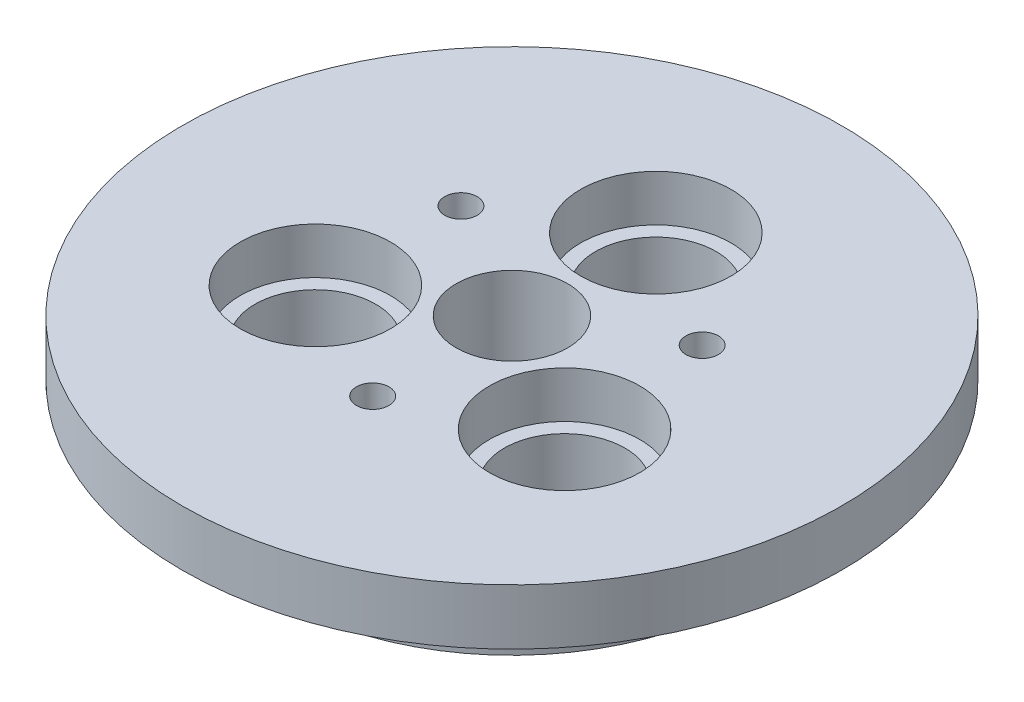
SolidWorks part; units mm, degrees
ref_plane "Front Plane" through (0, 0, 0) normal (0, 0, 1) x (1, 0, 0)
ref_plane "Top Plane" through (0, 0, 0) normal (0, 1, 0) x (1, 0, 0)
ref_plane "Right Plane" through (0, 0, 0) normal (1, 0, 0) x (0, 0, -1)
sketch "Sketch1" plane through (0, 0, 0) normal (0, 1, 0) x (1, 0, 0)
  circle A0 centre (0, 0) radius 35.5
  dimension "D1" = 71
extrude "Boss-Extrude1" add sketch "Sketch1" along normal mid plane 6
sketch "Sketch2" plane through (0, 3, 0) normal (0, 1, 0) x (1, 0, 0)
  circle A0 centre (0, 0) radius 26
  dimension "D1" = 52
extrude "Boss-Extrude2" add sketch "Sketch2" along normal blind 1
sketch "Sketch3" plane through (0, 4, 0) normal (0, 1, 0) x (1, 0, 0)
  circle A0 centre (0, 0) radius 25
  dimension "D1" = 50
extrude "Boss-Extrude3" add sketch "Sketch3" along normal blind 19
sketch "Sketch4" plane through (0, 23, 0) normal (0, 1, 0) x (1, 0, 0)
  line L0 (0, 15.5) -> (0, 0) construction
  line L1 (0, 0) -> (-13.4234, -7.75) construction
  circle A0 centre (0, 15.5) radius 12
  circle A1 centre (13.4234, -7.75) radius 12
  circle A2 centre (-13.4234, -7.75) radius 12
  dimension "D1" = 24
  dimension "D2" = 15.5
  dimension "D3" = 3
extrude "Cut-Extrude1" [suppressed] cut sketch "Sketch4" against normal through all
sketch "Sketch5" plane through (0, 23, 0) normal (0, 1, 0) x (1, 0, 0)
  circle A0 centre (0, 0) radius 6
  dimension "D1" = 12
extrude "Cut-Extrude2" cut sketch "Sketch5" against normal through all
fillet "Fillet1" [suppressed] radius 1
sketch "Sketch6" plane through (0, 23, 0) normal (0, 1, 0) x (1, 0, 0)
  circle A0 centre (0, 0) radius 30.0189
  circle A1 centre (0, 0) radius 20
  dimension "D1" = 40
extrude "Cut-Extrude3" cut sketch "Sketch6" against normal blind 12
chamfer "Chamfer2" distance 2.5 angle 45 1 edges at (0, 11, 20)
sketch "Sketch8" plane through (0, -3, 0) normal (0, -1, 0) x (1, 0, 0)
  circle A0 centre (0, 0) radius 25
  dimension "D1" = 50
extrude "Boss-Extrude4" add sketch "Sketch8" along normal blind 8
sketch "Sketch10" plane through (0, -11, 0) normal (0, -1, 0) x (1, 0, 0)
  circle A0 centre (0, 0) radius 6
  dimension "D1" = 12
extrude "Cut-Extrude6" cut sketch "Sketch10" against normal through all
sketch "Sketch7" plane through (0, 23, 0) normal (0, 1, 0) x (1, 0, 0)
  circle A0 centre (0, -15) radius 1.75
  circle A1 centre (-12.9904, 7.5) radius 1.75
  circle A2 centre (12.9904, 7.5) radius 1.75
  dimension "D1" = 15
  dimension "D2" = 3.5
  dimension "D3" = 3
extrude "Cut-Extrude4" cut sketch "Sketch7" against normal through all
sketch "Sketch11" plane through (0, -3, 0) normal (0, -1, 0) x (1, 0, 0)
  circle A0 centre (0, 0) radius 26
  circle A1 centre (0, 0) radius 25 construction
  circle A2 centre (0, 0) radius 25
  dimension "D1" = 1
extrude "Boss-Extrude5" add sketch "Sketch11" along normal blind 1
sketch "Sketch9" [suppressed] plane through (0, -9.5, 0) normal (0, -1, 0) x (1, 0, 0)
  circle A0 centre (-13.4234, 7.75) radius 12
  circle A1 centre (13.4234, 7.75) radius 12
  circle A2 centre (0, -15.5) radius 12
  dimension "D1" = 24
  dimension "D2" = 3
extrude "Cut-Extrude5" [suppressed] cut sketch "Sketch9" against normal through all
chamfer "Chamfer1" distance 1 angle 45 2 edges at (0, -3, 26) (0, 3, 26)
sketch "Sketch12" plane through (0, 0, 0) normal (0, 0, 1) x (1, 0, 0)
  line L0 (35.5, 3) -> (-35.5, 3) construction
  line L1 (-43.9976, 30.5246) -> (48.2592, 30.5246)
  line L2 (-43.9976, 30.5246) -> (-43.9976, 3)
  line L3 (-43.9976, 3) -> (48.2592, 3)
  line L4 (48.2592, 30.5246) -> (48.2592, 3)
extrude "Cut-Extrude7" cut sketch "Sketch12" against normal through all both and the other way through all
sketch "Sketch13" [suppressed] plane through (0, 1.5, 0) normal (0, 1, 0) x (1, 0, 0)
  circle A1 centre (13.4234, -7.75) radius 12
  circle A2 centre (13.4234, -7.75) radius 8
  arc A3 (1.4297, -7.3625) -> (7.0909, 2.4431) centre (13.4234, -7.75) ccw construction
  circle A4 centre (-13.4234, -7.75) radius 12
  circle A5 centre (-13.4234, -7.75) radius 8
  circle A6 centre (0, 15.5) radius 12
  circle A7 centre (0, 15.5) radius 8
  point P7 (0, 0)
  point P8 (0, 0)
  dimension "D1" = 16
  dimension "D2" = 3
sketch "Sketch14" plane through (0, 3, 0) normal (0, 1, 0) x (1, 0, 0)
  line L0 (0, 15.5) -> (0, 0) construction
  line L1 (0, 0) -> (-13.4234, -7.75) construction
  circle A0 centre (0, 15.5) radius 8.1
  circle A1 centre (0, 0) radius 6 construction
  circle A2 centre (13.4234, -7.75) radius 8.1
  circle A3 centre (-13.4234, -7.75) radius 8.1
  dimension "D1" = 16.2
  dimension "D2" = 15.5
  dimension "D3" = 3
extrude "Cut-Extrude8" cut sketch "Sketch14" against normal blind 5
sketch "Sketch15" plane through (0, -2, 0) normal (0, 1, 0) x (1, 0, 0)
  circle A0 centre (0, 15.5) radius 6.5
  circle A1 centre (13.4234, -7.75) radius 6.5
  circle A2 centre (-13.4234, -7.75) radius 6.5
  dimension "D1" = 13
extrude "Cut-Extrude9" cut sketch "Sketch15" against normal through all
